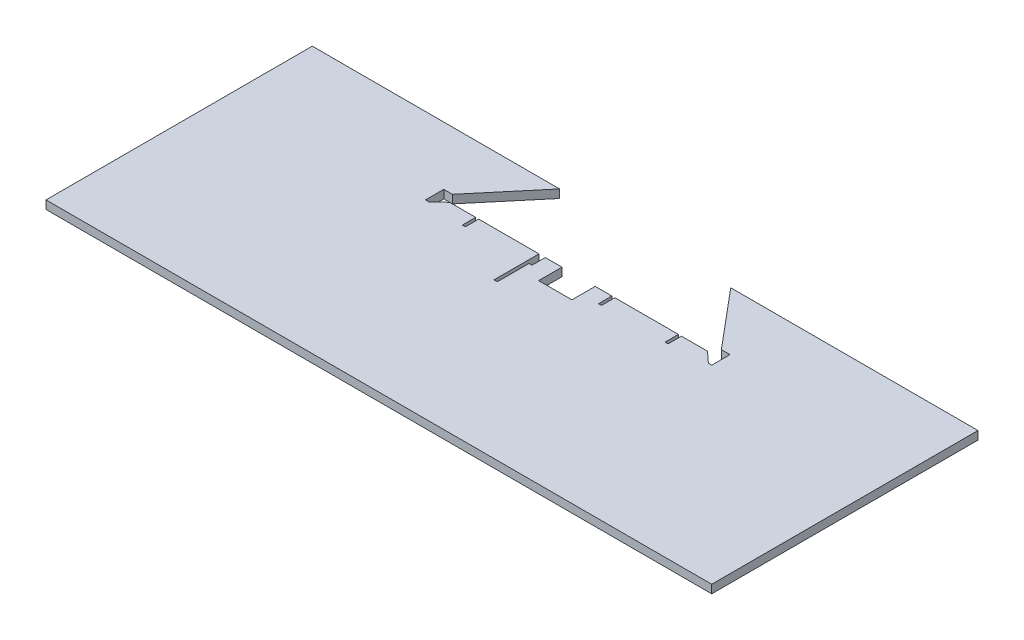
SolidWorks part; units mm, degrees
material "Depron"
ref_plane "Front Plane" through (0, 0, 0) normal (0, 0, 1) x (1, 0, 0)
ref_plane "Top Plane" through (0, 0, 0) normal (0, 1, 0) x (1, 0, 0)
ref_plane "Right Plane" through (0, 0, 0) normal (1, 0, 0) x (0, 0, -1)
sketch "Sketch1" plane through (0, 0, 0) normal (0, 1, 0) x (1, 0, 0)
  line L0 (32.6619, 101.6) -> (127, 101.6)
  line L1 (-127, 0) -> (127, 0)
  line L2 (-127, 0) -> (-127, 101.6)
  line L3 (-127, 101.6) -> (-32.6619, 101.6)
  line L4 (127, 0) -> (127, 101.6)
  line L5 (0, -898.4) -> (0, 49101.6) construction
  line L6 (-53.975, 76.2) -> (-32.6619, 101.6)
  line L7 (-53.975, 76.2) -> (53.975, 76.2)
  line L8 (53.975, 76.2) -> (32.6619, 101.6)
  line L9 (-1003.9539, 76.2) -> (48996.0461, 76.2) construction
  point P11 (0, 76.2)
  dimension "D1" = 101.6
  dimension "D2" = 254
  dimension "D4" = 107.95
  dimension "D6" = 25.4
extrude "Boss-Extrude1" add sketch "Sketch1" along normal blind 3.175
sketch "Sketch2" plane through (0, 3.175, 0) normal (0, 1, 0) x (-1, 0, 0)
  line L0 (0, 0) -> (0, -134.62) construction
  line L1 (127, 0) -> (-127, 0) construction
  line L2 (-53.975, -76.2) -> (53.975, -76.2) construction
  line L3 (39.243, -76.2) -> (38.1, -76.2)
  line L4 (39.243, -76.2) -> (39.243, -71.12)
  line L5 (39.243, -71.12) -> (38.1, -71.12)
  line L6 (38.1, -76.2) -> (38.1, -71.12)
  line L7 (13.843, -76.2) -> (12.7, -76.2)
  line L8 (-53.975, -76.2) -> (53.975, -76.2) construction
  line L9 (13.843, -71.12) -> (12.7, -71.12)
  line L10 (12.7, -76.2) -> (12.7, -71.12)
  line L11 (-12.7, -76.2) -> (-12.7, -71.12)
  line L12 (-13.843, -71.12) -> (-12.7, -71.12)
  line L13 (-13.843, -76.2) -> (-13.843, -71.12)
  line L14 (-13.843, -76.2) -> (-12.7, -76.2)
  line L15 (-38.1, -76.2) -> (-38.1, -71.12)
  line L16 (-39.243, -71.12) -> (-38.1, -71.12)
  line L17 (-39.243, -76.2) -> (-39.243, -71.12)
  line L18 (-39.243, -76.2) -> (-38.1, -76.2)
  line L19 (6.35, -76.2) -> (-6.35, -76.2)
  line L20 (13.843, -76.2) -> (15.113, -76.2)
  line L21 (13.843, -71.12) -> (13.843, -59.055)
  line L22 (13.843, -59.055) -> (15.113, -59.055)
  line L23 (15.113, -76.2) -> (15.113, -59.055)
  line L24 (6.35, -76.2) -> (6.35, -67.31)
  line L25 (6.35, -67.31) -> (-6.35, -67.31)
  line L26 (-6.35, -76.2) -> (-6.35, -67.31)
  line L27 (-53.975, -76.2) -> (-51.3109, -79.375)
  line L28 (53.34, -80.01) -> (54.61, -80.01) construction
  line L29 (53.34, -80.01) -> (53.34, -72.39) construction
  line L30 (53.34, -72.39) -> (54.61, -72.39)
  line L31 (54.61, -80.01) -> (54.61, -72.39) construction
  line L32 (53.34, -80.01) -> (54.61, -72.39) construction
  line L33 (53.34, -72.39) -> (54.61, -80.01) construction
  line L34 (-53.34, -76.2) -> (-53.975, -76.2)
  line L35 (-53.34, -72.39) -> (-49.1905, -76.2)
  line L36 (-53.34, -72.39) -> (-54.61, -72.39)
  line L37 (53.975, -76.2) -> (32.6619, -101.6) construction
  line L38 (53.975, -76.2) -> (51.3109, -79.375)
  line L39 (51.3109, -79.375) -> (54.61, -79.375)
  line L40 (54.61, -79.375) -> (54.61, -72.39)
  line L41 (53.34, -72.39) -> (49.1905, -76.2)
  line L42 (53.34, -76.2) -> (53.975, -76.2)
  line L43 (-54.61, -79.375) -> (-54.61, -72.39)
  line L44 (-51.3109, -79.375) -> (-54.61, -79.375)
  point P31 (0, -67.31)
  point P32 (53.975, -76.2)
  line M6 (-53.975, -76.2) -> (53.975, -76.2)
  line M38 (-32.6619, -101.6) -> (-53.975, -76.2)
  line M39 (53.975, -76.2) -> (32.6619, -101.6)
  dimension "D1" = 1.143
  dimension "D2" = 5.08
  dimension "D3" = 1.143
  dimension "D4" = 5.08
  dimension "D5" = 1.27
  dimension "D6" = 17.145
  dimension "D7" = 12.7
  dimension "D8" = 38.1
  dimension "D9" = 12.7
  dimension "D10" = 8.89
  dimension "D11" = 1.27
  dimension "D12" = 7.62
  dimension "D13" = 3.175
  dimension "D14" = 4.7845
ref_plane "Center Plane" through (0, 0, 0) normal (1, 0, 0) x (0, 0, -1)
sketch "Sketch3" plane through (0, 3.175, 0) normal (0, 1, 0) x (1, 0, 0)
  line L0 (-38.6715, 71.12) -> (-38.6715, 76.2)
  line L1 (-39.243, 71.12) -> (-38.1, 71.12) construction
  line L2 (-39.243, 76.2) -> (-38.1, 76.2) construction
  line L3 (-14.478, 76.2) -> (-14.478, 59.055)
  line L4 (-13.843, 76.2) -> (-15.113, 76.2) construction
  line L5 (-13.843, 59.055) -> (-15.113, 59.055) construction
  line L6 (-13.2715, 71.12) -> (-13.2715, 76.2)
  line L7 (-13.843, 71.12) -> (-12.7, 71.12) construction
  line L8 (-13.843, 76.2) -> (-12.7, 76.2) construction
  line L9 (-6.35, 76.2) -> (-6.35, 67.31)
  line L10 (-6.35, 67.31) -> (6.35, 67.31)
  line L11 (6.35, 67.31) -> (6.35, 76.2)
  line L12 (13.2715, 71.12) -> (13.2715, 76.2)
  line L13 (13.843, 71.12) -> (12.7, 71.12) construction
  line L14 (13.843, 76.2) -> (12.7, 76.2) construction
  line L15 (38.6715, 71.12) -> (38.6715, 76.2)
  line L16 (39.243, 71.12) -> (38.1, 71.12) construction
  line L17 (39.243, 76.2) -> (38.1, 76.2) construction
extrude "Cut-Extrude1" cut sketch "Sketch2" against normal up to surface (3.175 mm away) contours L6 L4 L5 M6 | L23 L22 L21 L9 L10 M6 | L26 L24 L25 M6 | L13 L11 L12 M6 | L17 L15 L16 M6 | L39 L40 L30 M6 M39 | L44 L36 L43 M38 M6 region at (52.9708, 3.175, -75.8259) region at (38.6715, 3.175, -73.66) region at (13.2715, 3.175, -73.66) region at (0, 3.175, -71.755) region at (-14.224, 3.175, -68.8975) region at (-38.6715, 3.175, -73.66) region at (-52.9708, 3.175, -75.8259) up to face at (0, 0, -69.85)
